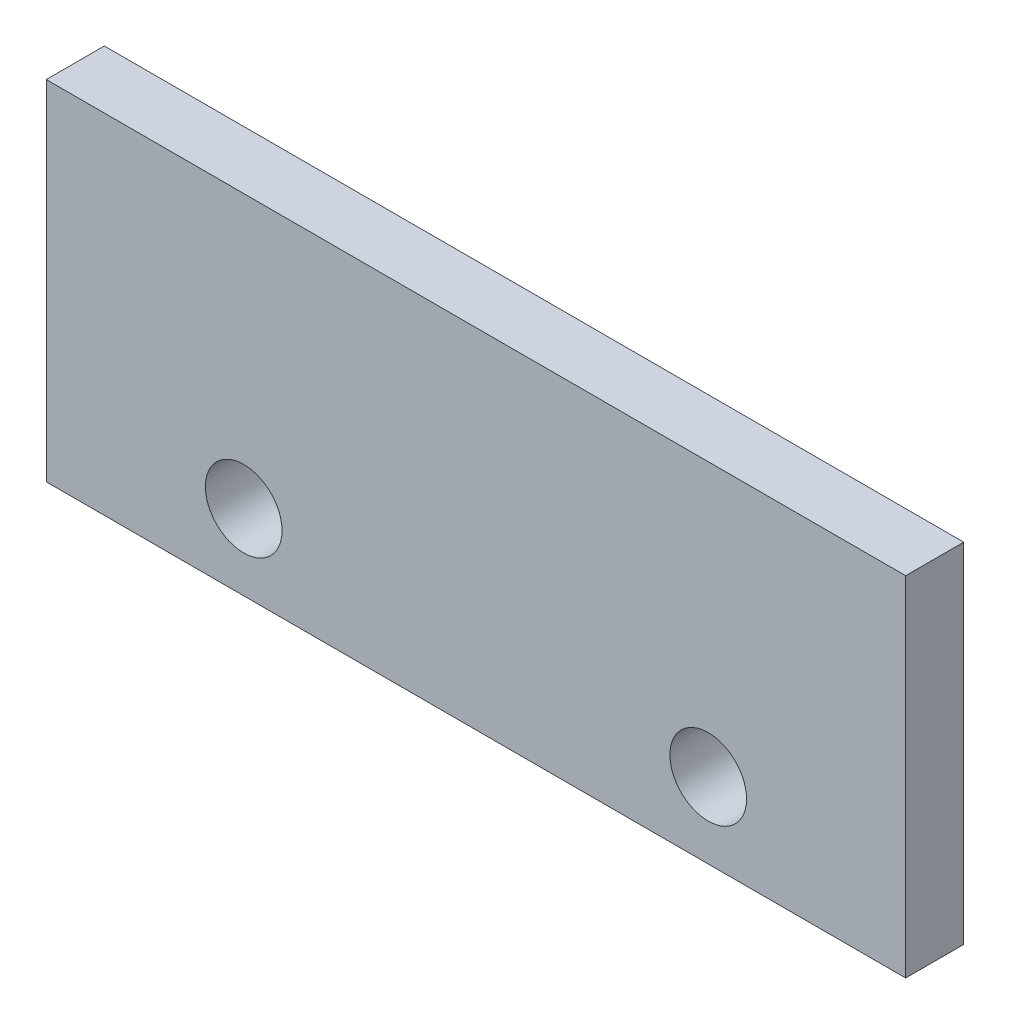
SolidWorks part; units mm, degrees
ref_plane "Top" through (0, 0, 0) normal (0, 0, 1) x (1, 0, 0)
ref_plane "Front" through (0, 0, 0) normal (0, 1, 0) x (1, 0, 0)
ref_plane "Right" through (0, 0, 0) normal (1, 0, 0) x (0, 0, -1)
sketch "Sketch1" plane through (0, 0, 0) normal (0, 0, 1) x (1, 0, 0)
  line L1 (0, 0) -> (74, 0)
  line L2 (0, 0) -> (0, 30)
  line L3 (0, 30) -> (74, 30)
  line L4 (74, 0) -> (74, 30)
  dimension "D1" = 30
  dimension "D2" = 74
extrude "Boss-Extrude1" add sketch "Sketch1" along normal blind 5
sketch "Sketch2" plane through (0, 0, 5) normal (0, 0, 1) x (1, 0, 0)
  line L0 (17, 6.5) -> (57, 6.5)
  line L1 (0, 0) -> (74, 0) construction
  line L2 (74, 0) -> (74, 30) construction
  dimension "D1" = 6.5
  dimension "D2" = 40
  dimension "D3" = 17
hole_wizard "M6 Clearance Hole1" positions "Sketch3" profile "Sketch4" hole size "M6" standard "DIN" end condition through all
sketch "Sketch3" plane through (0, 0, 5) normal (0, 0, 1) x (1, 0, 0)
  point P0 (17, 6.5)
  point P3 (57, 6.5)
sketch "Sketch4" plane through (17, 6.5, 5) normal (1, 0, 0) x (0, -1, 0)
  line L0 (0, 0) -> (0, 5)
  line L1 (0, 5) -> (3.3, 5)
  line L2 (3.3, 5) -> (3.3, 0)
  line L5 (3.3, 0) -> (0, 0)
  line L11 (0, -6.35) -> (0, 107.95) construction
  dimension "Thru Hole Dia." = 6.6
  dimension "Thru Hole Depth" = 5
